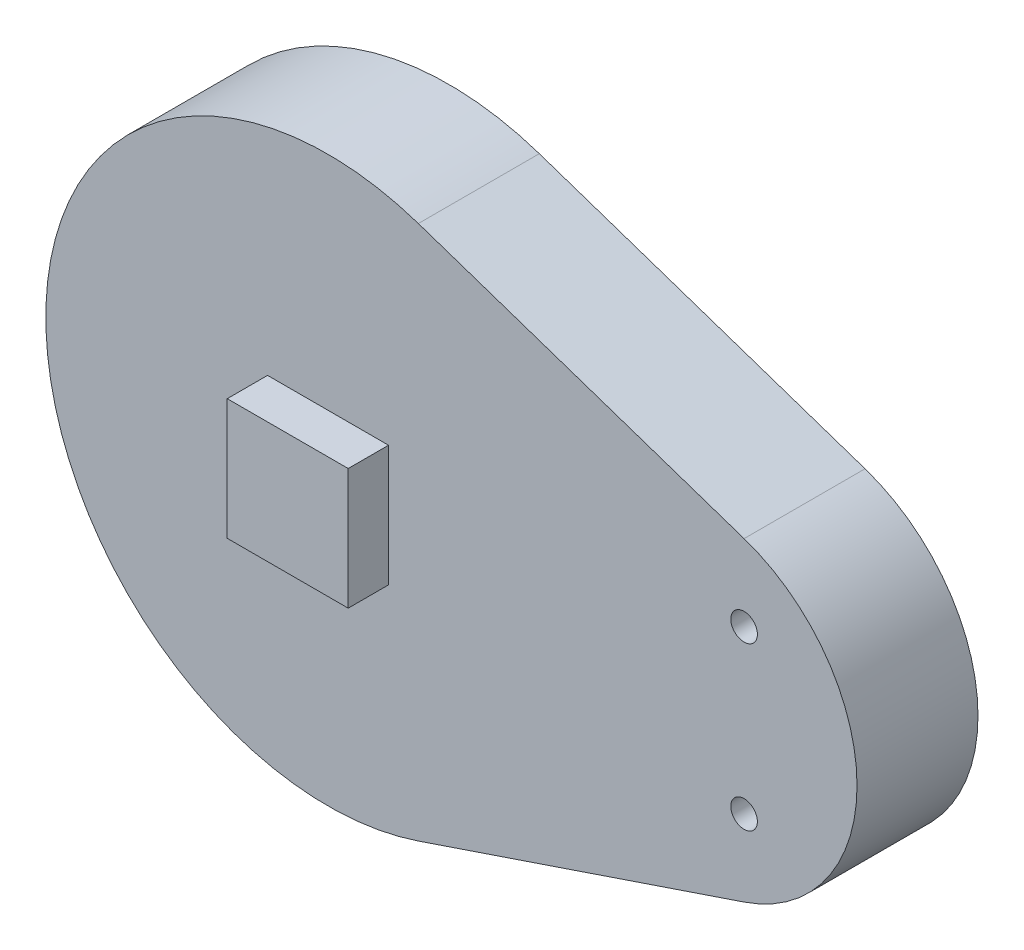
SolidWorks part; units mm, degrees
ref_plane "Płaszczyzna przednia" through (0, 0, 0) normal (0, 0, 1) x (1, 0, 0)
ref_plane "Płaszczyzna górna" through (0, 0, 0) normal (0, 1, 0) x (1, 0, 0)
ref_plane "Płaszczyzna prawa" through (0, 0, 0) normal (1, 0, 0) x (0, 0, -1)
sketch "Szkic1" plane through (0, 0, 0) normal (0, 0, 1) x (1, 0, 0)
  line L0 (45.0324, 65.8874) -> (-35.7516, 93.173)
  line L1 (31.8484, 26.8538) -> (-9.3516, 26.8538) construction
  line L2 (45.0324, -12.1798) -> (-35.7516, -39.4655)
  arc A0 (-35.7516, 93.173) -> (-35.7516, -39.4655) centre (-58.1516, 26.8538) ccw
  arc A1 (45.0324, -12.1798) -> (45.0324, 65.8874) centre (31.8484, 26.8538) ccw
  dimension "D1" = 140
  dimension "D2" = 90
extrude "Dodanie-wyciągnięcie1" add sketch "Szkic1" against normal blind 30
sketch "Szkic2" plane through (0, 0, 0) normal (0, 0, 1) x (1, 0, 0)
  line L1 (-43.1516, 11.8538) -> (-73.1516, 11.8538)
  line L2 (-43.1516, 11.8538) -> (-43.1516, 41.8538)
  line L3 (-43.1516, 41.8538) -> (-73.1516, 41.8538)
  line L4 (-73.1516, 11.8538) -> (-73.1516, 41.8538)
  line L5 (-43.1516, 11.8538) -> (-73.1516, 41.8538) construction
  line L6 (-43.1516, 41.8538) -> (-73.1516, 11.8538) construction
  point P0 (-58.1516, 26.8538)
  dimension "D1" = 30
  dimension "D2" = 30
extrude "Dodanie-wyciągnięcie2" add sketch "Szkic2" along normal blind 10
sketch "Szkic3" plane through (0, 0, -30) normal (0, 0, -1) x (-1, 0, 0)
  circle A0 centre (58.1516, 26.8538) radius 65
extrude "Dodanie-wyciągnięcie3" add sketch "Szkic3" along normal blind 3
sketch "Szkic4" plane through (0, 0, -30) normal (0, 0, -1) x (-1, 0, 0)
  line L0 (-45.0324, -12.1798) -> (-45.0324, 65.8874) construction
  line L1 (-45.0324, 65.8874) -> (-73.0484, 26.8538) construction
  line L2 (-73.0484, 26.8538) -> (-45.0324, 6.7456) construction
  arc A0 (-45.0324, 65.8874) -> (-45.0324, -12.1798) centre (-31.8484, 26.8538) ccw construction
  point P10 (-45.0324, 6.7456)
hole_wizard "Pogłębienie walcowe pod M6 Śrubę z łbem stożkowym ściętym1" positions "Szkic 3D1" profile "Szkic5" counterbore size "M6" standard "ISO" end condition up to next
sketch3d "Szkic 3D1"
  point P0 (45.0324, 6.7456, -30)
sketch "Szkic5" plane through (45.0324, 6.7456, -30) normal (1, 0, 0) x (0, 1, 0)
  line L0 (0, 0) -> (0, 30)
  line L1 (0, 30) -> (3.3, 30)
  line L3 (3.3, 30) -> (3.3, 4.6)
  line L4 (3.3, 4.6) -> (6.5, 4.6)
  line L5 (6.5, 4.6) -> (6.5, 0)
  line L7 (6.5, 0) -> (0, 0)
  line L11 (0, -6.35) -> (0, 107.95) construction
  dimension "Średnica otworu na wylot" = 6.6
  dimension "Głębokość otworu na wylot" = 30
  dimension "Średnica pogłębienia walcowego" = 13
  dimension "Głębokość pogłębienia walcowego" = 4.6
sketch "Szkic6" plane through (0, 0, -30) normal (0, 0, -1) x (-1, 0, 0)
  line L0 (-45.0324, -12.1798) -> (-45.0324, 65.8874) construction
  line L1 (-45.0324, 65.8874) -> (-73.0484, 26.8538) construction
  line L2 (-73.0484, 26.8538) -> (-45.0324, 46.962) construction
  line L5 (-73.0484, 26.8538) -> (-45.0324, 6.7456) construction
  line L6 (-45.0324, 6.7456) -> (-45.0324, 26.8538) construction
  line L7 (-45.0324, 26.8538) -> (-73.0484, 26.8538) construction
  point P8 (-45.0324, 46.962)
hole_wizard "Pogłębienie walcowe pod M6 Śrubę z łbem stożkowym ściętym2" positions "Szkic 3D2" profile "Szkic7" counterbore size "M6" standard "ISO" end condition up to next
sketch3d "Szkic 3D2"
  point P0 (45.0324, 46.962, -30)
sketch "Szkic7" plane through (45.0324, 46.962, -30) normal (1, 0, 0) x (0, 1, 0)
  line L0 (0, 0) -> (0, 30)
  line L1 (0, 30) -> (3.3, 30)
  line L3 (3.3, 30) -> (3.3, 4.6)
  line L4 (3.3, 4.6) -> (6.5, 4.6)
  line L5 (6.5, 4.6) -> (6.5, 0)
  line L7 (6.5, 0) -> (0, 0)
  line L11 (0, -6.35) -> (0, 107.95) construction
  dimension "Średnica otworu na wylot" = 6.6
  dimension "Głębokość otworu na wylot" = 30
  dimension "Średnica pogłębienia walcowego" = 13
  dimension "Głębokość pogłębienia walcowego" = 4.6
fillet "Zaokrąglenie2" radius 1 2 edges at (38.5324, 46.962, -30) (38.5324, 6.7456, -30)
sketch "Szkic8" plane through (0, 0, -33) normal (0, 0, -1) x (-1, 0, 0)
  circle A0 centre (58.1516, 26.8538) radius 30
extrude "Wytnij-wyciągnięcie1" cut sketch "Szkic8" against normal blind 10
